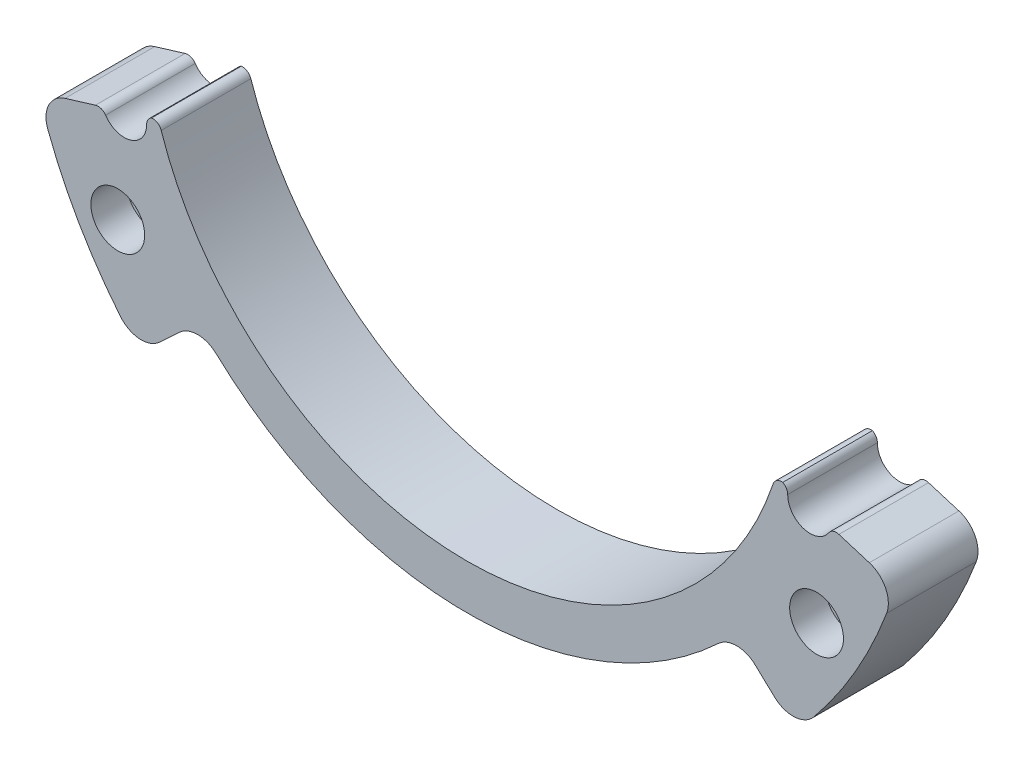
SolidWorks part; units mm, degrees
material "ABS"
ref_plane "前视基准面" through (0, 0, 0) normal (0, 0, 1) x (1, 0, 0)
ref_plane "上视基准面" through (0, 0, 0) normal (0, 1, 0) x (1, 0, 0)
ref_plane "右视基准面" through (0, 0, 0) normal (1, 0, 0) x (0, 0, -1)
sketch "草图1" plane through (0, 0, 0) normal (0, 0, 1) x (1, 0, 0)
  line L0 (-34.427, -10.5254) -> (-47.8152, -14.6186)
  line L1 (34.427, -10.5254) -> (47.8152, -14.6186)
  line L2 (0, 32.265) -> (0, -133.7868) construction
  line L4 (29.9855, -27.9619) -> (36.5677, -34.0999)
  line L5 (0, 0) -> (-43.3013, -25) construction
  line L6 (0, 0) -> (43.3013, -25) construction
  line L7 (-29.9855, -27.9619) -> (-36.5677, -34.0999)
  arc A0 (-47.8152, -14.6186) -> (47.8152, -14.6186) centre (0, 0) ccw construction
  arc A1 (-29.9855, -27.9619) -> (29.9855, -27.9619) centre (0, 0) ccw
  arc A2 (-34.427, -10.5254) -> (34.427, -10.5254) centre (0, 0) ccw
  arc A3 (-47.8152, -14.6186) -> (-36.5677, -34.0999) centre (0, 0) ccw
  arc A4 (36.5677, -34.0999) -> (47.8152, -14.6186) centre (0, 0) ccw
  arc A5 (-38.9711, -22.5) -> (38.9711, -22.5) centre (0, 0) ccw construction
  circle A6 centre (-38.9711, -22.5) radius 1.6
  circle A7 centre (38.9711, -22.5) radius 1.6
  dimension "D2" = 120
  dimension "D3" = 26
  dimension "D4" = 50
  dimension "D5" = 41
  dimension "D6" = 36
  dimension "D7" = 13
  dimension "D8" = 45
  dimension "D9" = 3.2
  dimension "D1" = 26
extrude "凸台-拉伸1" add sketch "草图1" along normal blind 10
sketch "草图2" plane through (0, 0, 10) normal (0, 0, 1) x (1, 0, 0)
  line L0 (-34.427, -10.5254) -> (-47.8152, -14.6186) construction
  line L1 (0, 8.4058) -> (0, -54.0224) construction
  circle A0 centre (-38.2522, -11.6949) radius 2.5
  circle A1 centre (38.2522, -11.6949) radius 2.5
  dimension "D2" = 5
  dimension "D1" = 40
extrude "切除-拉伸1" cut sketch "草图2" against normal through all
sketch "草图3" plane through (0, 0, 10) normal (0, 0, 1) x (1, 0, 0)
  circle A0 centre (-38.9711, -22.5) radius 3
  circle A1 centre (38.9711, -22.5) radius 3
  dimension "D1" = 6
  dimension "D2" = 6
extrude "切除-拉伸2" cut sketch "草图3" against normal blind 4
fillet "圆角4" radius 1 6 edges at (40.643, -12.4258, 5) (35.8614, -10.9639, 5) (34.427, -10.5254, 5) (-40.643, -12.4258, 5) (-35.8614, -10.9639, 5) (-34.427, -10.5254, 5)
fillet "圆角5" radius 3 6 edges at (-47.8152, -14.6186, 5) (-36.5677, -34.0999, 5) (-29.9855, -27.9619, 5) (36.5677, -34.0999, 5) (29.9855, -27.9619, 5) (47.8152, -14.6186, 5)
